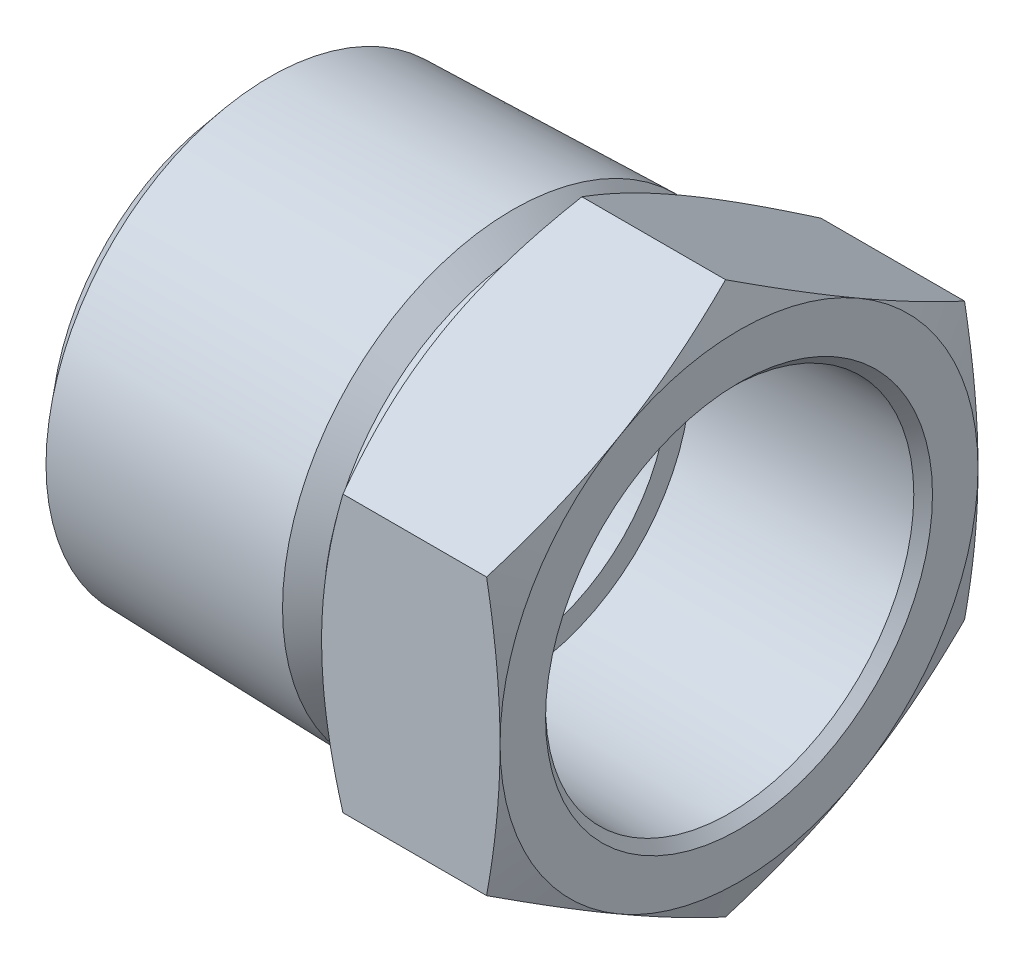
SolidWorks part; units mm, degrees
ref_plane "Front" through (0, 0, 0) normal (0, 0, 1) x (1, 0, 0)
ref_plane "Top" through (0, 0, 0) normal (0, 1, 0) x (1, 0, 0)
ref_plane "Right" through (0, 0, 0) normal (1, 0, 0) x (0, 0, -1)
sketch "Sketch1" plane through (0, 0, 0) normal (0, 0, 1) x (1, 0, 0)
  line L0 (-9.525, 0) -> (9.525, 0) construction
  point P3 (20.193, 0)
ref_plane "Plane1" through (-9.525, 0, 0) normal (1, 0, 0) x (0, 0, -1)
sketch "Sketch2" plane through (-9.525, 0, 0) normal (1, 0, 0) x (0, 0, -1)
  circle A0 centre (0, 0) radius 13.335
  dimension "pipe OD" = 26.67
extrude "Extrude1" add sketch "Sketch2" along normal up to vertex (19.05 mm away) draft 1.5 up to point (9.525, 0, 0) draft outward yes
sketch "Sketch6" plane through (-9.525, 0, 0) normal (-1, 0, 0) x (0, 0, 1)
  circle A0 centre (0, 0) radius 13.335 construction
  circle A1 centre (0, 0) radius 13.335
curve "Helix/Spiral1" parameters "pitch"=1.8143
sketch "Sketch7" plane through (0, 0, 0) normal (0, 0, 1) x (1, 0, 0)
  line L0 (-10.3188, 13.335) -> (-9.6384, 12.1566)
  line L1 (-9.6384, 12.1566) -> (-9.4116, 12.1566)
  line L2 (-9.4116, 12.1566) -> (-8.7312, 13.335) construction
  line L3 (-10.3188, 13.335) -> (-8.7312, 13.335) construction
  line L4 (-9.525, 13.335) -> (-9.525, 12.1566) construction
  line L5 (-9.9786, 12.7458) -> (-9.0714, 12.7458) construction
  line L6 (-10.3188, 13.335) -> (-8.5513, 13.6466)
  line L7 (-9.4116, 12.1566) -> (-8.5513, 13.6466)
  line L9 (-9.525, 13.335) -> (-9.525, -13.335) construction
  dimension "D1" = 60
  dimension "D2" = 0.2268
  dimension "D3" = 0.9071
  dimension "D4" = 10
sweep "Cut-Sweep1" [suppressed] cut profiles "Sketch7" path "Helix/Spiral1"
sketch "Sketch8" plane through (0, 0, 0) normal (0, 0, 1) x (1, 0, 0)
  line L0 (-9.525, 14.2816) -> (-9.525, 11.3946)
  line L1 (-9.525, 11.3946) -> (-7.1025, 14.2816)
  line L2 (-9.525, 14.2816) -> (-7.1025, 14.2816)
  line L3 (-9.525, -50) -> (-9.525, 50) construction
  line L4 (9.525, 12.5284) -> (9.525, 14.2816)
  line L5 (9.525, 12.5284) -> (7.8921, 12.5284)
  line L6 (7.8921, 12.5284) -> (6.1389, 14.2816)
  line L7 (6.1389, 14.2816) -> (9.525, 14.2816)
  line L8 (-9.525, 12.1566) -> (9.525, 12.6554) construction
  line L9 (-9.9786, 12.7458) -> (-9.0714, 12.7458) construction
  dimension "D1" = 50
  dimension "D2" = 0.762
  dimension "D3" = 0.635
  dimension "D4" = 45
  dimension "D5" = 1.6329
  dimension "D6" = 1.5
  dimension "D7" = 0.127
revolve "Cut-Revolve1" cut sketch "Sketch8" angle 360 about L0
sketch "Sketch3" plane through (9.525, 0, 0) normal (1, 0, 0) x (0, 0, -1)
  line L1 (14.2875, 8.2489) -> (0, 16.4978)
  line L2 (0, 16.4978) -> (-14.2875, 8.2489)
  line L3 (-14.2875, 8.2489) -> (-14.2875, -8.2489)
  line L4 (-14.2875, -8.2489) -> (0, -16.4978)
  line L5 (0, -16.4978) -> (14.2875, -8.2489)
  line L6 (14.2875, -8.2489) -> (14.2875, 8.2489)
  circle A0 centre (0, 0) radius 14.2875 construction
  dimension "Hex" = 28.575
extrude "Extrude2" add sketch "Sketch3" along normal up to vertex (10.668 mm away) up to point (20.193, 0, 0)
sketch "Sketch4" plane through (20.193, 0, 0) normal (1, 0, 0) x (0, 0, -1)
  circle A0 centre (0, 0) radius 14.2875 construction
  circle A1 centre (0, 0) radius 14.2875
extrude "Cut-Extrude1" cut sketch "Sketch4" against normal through all draft 70 flip side to cut
sketch "Sketch23" plane through (9.525, 0, 0) normal (-1, 0, 0) x (0, 0, 1)
  circle A1 centre (0, 0) radius 14.2875
  circle A2 centre (0, 0) radius 14.2875
  dimension "D1" = 0
extrude "Cut-Extrude7" cut sketch "Sketch23" against normal through all draft 60 flip side to cut
ref_plane "Plane2" through (6.637, 0, 0) normal (1, 0, 0) x (0, 0, -1)
sketch "Sketch15" plane through (6.637, 0, 0) normal (1, 0, 0) x (0, 0, -1)
  circle A0 centre (0, 0) radius 10.668
  dimension "female id" = 21.336
extrude "Cut-Extrude2" cut sketch "Sketch15" along normal through all draft 1.5 draft outward yes
sketch "Sketch18" plane through (20.193, 0, 0) normal (1, 0, 0) x (0, 0, -1)
  circle A2 centre (0, 0) radius 11.5673
  circle A3 centre (0, 0) radius 11.5673
  dimension "D1" = 0.5443
sketch "Sketch16" plane through (6.637, 0, 0) normal (1, 0, 0) x (0, 0, -1)
  circle A0 centre (0, 0) radius 10.668 construction
  circle A1 centre (0, 0) radius 10.668
curve "Helix/Spiral2" parameters "pitch female"=1.8143
sketch "Sketch20" plane through (0, 0, 0) normal (0, 0, 1) x (1, 0, 0)
  line L0 (6.637, 10.668) -> (5.0495, 10.668) construction
  line L1 (5.0495, 10.668) -> (5.7299, 9.4896)
  line L2 (5.7299, 9.4896) -> (5.9567, 9.4896)
  line L3 (5.9567, 9.4896) -> (6.637, 10.668)
  line L4 (5.0495, 10.668) -> (6.8169, 10.9796)
  line L5 (6.637, 10.668) -> (6.8169, 10.9796)
  line L6 (5.8433, 10.668) -> (5.8433, 9.4896) construction
  line L7 (6.2968, 10.0788) -> (5.3897, 10.0788) construction
  line L8 (6.637, -10.668) -> (6.637, 10.668) construction
  dimension "D1" = 60
  dimension "D2" = 10
  dimension "D3" = 0.2268
  dimension "D4" = 0.9071
sweep "Sweep1" [suppressed] add profiles "Sketch20" path "Helix/Spiral2"
sketch "Sketch17" plane through (6.637, 0, 0) normal (1, 0, 0) x (0, 0, -1)
  arc A2 (9.3073, 0) -> (9.3073, 0) centre (0, 0) ccw
  circle A3 centre (0, 0) radius 9.3073
extrude "Cut-Extrude3" cut sketch "Sketch17" against normal through all
sketch "Sketch21" plane through (20.193, 0, 0) normal (1, 0, 0) x (0, 0, -1)
  circle A0 centre (0, 0) radius 14.2875 construction
  circle A1 centre (0, 0) radius 14.2875
extrude "Cut-Extrude5" [suppressed] cut sketch "Sketch21" along normal through all
extrude "Cut-Extrude6" cut sketch "Sketch18" against normal blind 6.35 draft 45
equation "\"D3@Helix/Spiral1\" = \"R@Sketch1\"+.250"
equation "\"D2@Sketch7\" = \"pitch@Helix/Spiral1\"*.125"
equation "\"D3@Sketch7\" = \"pitch@Helix/Spiral1\"*.5"
equation "\"D3@Helix/Spiral2\" = \"female depth@Plane2\"+.125"
equation "\"D1@Sketch17\" = \"pitch female@Helix/Spiral2\"*.75"
equation "\"D1@Sketch18\" = \"pitch female@Helix/Spiral2\"*.3"
equation "\"D3@Sketch20\" = \"pitch female@Helix/Spiral2\"*.125"
equation "\"D4@Sketch20\" = \"pitch female@Helix/Spiral2\"*.5"
equation "\"D5@Sketch8\" = \"pitch@Helix/Spiral1\"*.9"
